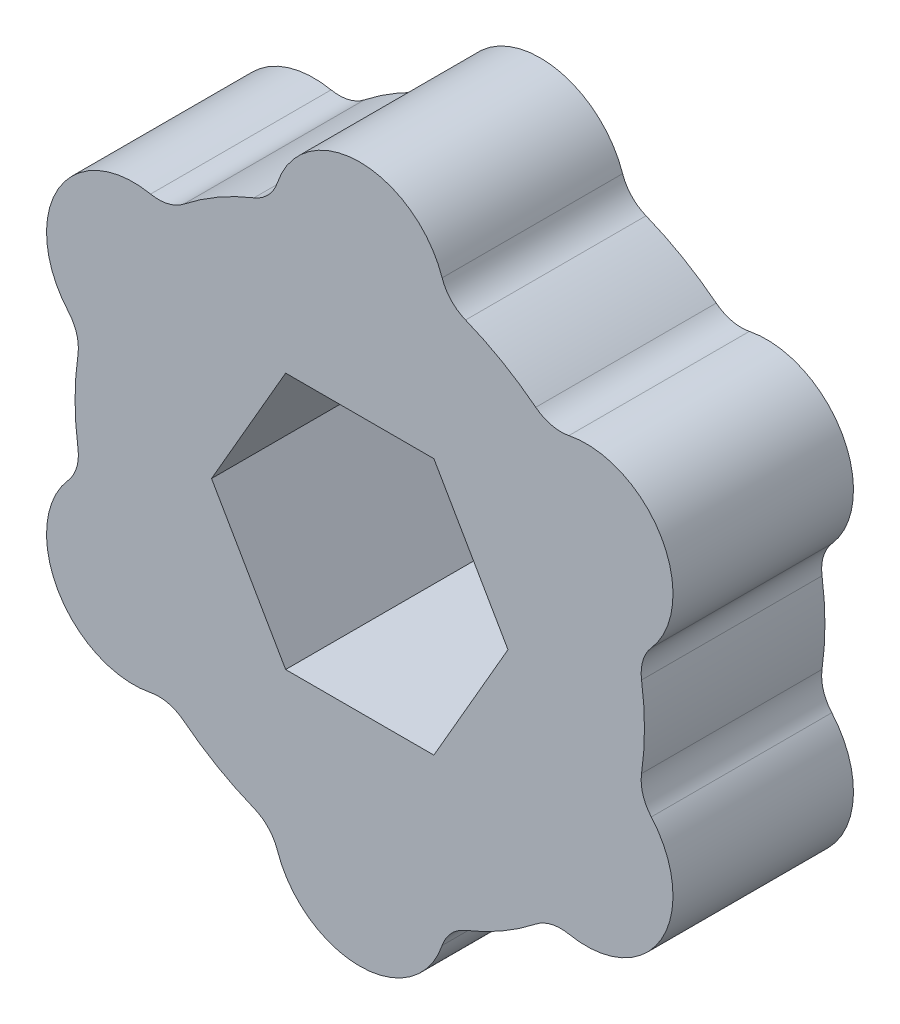
SolidWorks part; units mm, degrees
material "PET"
ref_plane "Front Plane" through (0, 0, 0) normal (0, 0, 1) x (1, 0, 0)
ref_plane "Top Plane" through (0, 0, 0) normal (0, 1, 0) x (1, 0, 0)
ref_plane "Right Plane" through (0, 0, 0) normal (1, 0, 0) x (0, 0, -1)
sketch "Sketch5" plane through (0, 0, 0) normal (0, 0, 1) x (1, 0, 0)
  line L0 (0, 0) -> (0, 13.0556) construction
  circle A0 centre (0, 0) radius 14.224
  circle A1 centre (0, 0) radius 17.399 construction
  arc A2 (-4.3147, 13.5538) -> (4.3147, 13.5538) centre (0, 13.0556) cw
  arc A3 (9.5806, 10.5136) -> (13.8953, 3.0402) centre (11.3065, 6.5278) cw
  arc A4 (13.8953, -3.0402) -> (9.5806, -10.5136) centre (11.3065, -6.5278) cw
  arc A5 (4.3147, -13.5538) -> (-4.3147, -13.5538) centre (0, -13.0556) cw
  arc A6 (-9.5806, -10.5136) -> (-13.8953, -3.0402) centre (-11.3065, -6.5278) cw
  arc A7 (-13.8953, 3.0402) -> (-9.5806, 10.5136) centre (-11.3065, 6.5278) cw
  point P24 (0, 0)
  dimension "D1" = 28.448
  dimension "D2" = 34.798
  dimension "D3" = 4.3434
  dimension "D4" = 6
extrude "Boss-Extrude2" add sketch "Sketch5" along normal blind 9.017 contours A7 A0 | A2 A0 | A3 A0 | A4 A0 | A5 A0 | A6 A0 | A0 region at (13.3495, 7.7073, 0) region at (13.3495, -7.7073, 0) region at (0, 15.4147, 0) region at (0, -15.4147, 0) region at (-13.3495, 7.7073, 0) region at (-13.3495, -7.7073, 0)
fillet "Fillet1" radius 2.032 12 edges at (-9.5806, 10.5136, 4.5085) (-4.3147, 13.5538, 4.5085) (4.3147, 13.5538, 4.5085) (9.5806, 10.5136, 4.5085) (13.8953, 3.0402, 4.5085) (13.8953, -3.0402, 4.5085) (9.5806, -10.5136, 4.5085) (4.3147, -13.5538, 4.5085) (-4.3147, -13.5538, 4.5085) (-9.5806, -10.5136, 4.5085) (-13.8953, -3.0402, 4.5085) (-13.8953, 3.0402, 4.5085)
sketch "Sketch6" plane through (0, 0, 9.017) normal (0, 0, 1) x (1, 0, 0)
  line L1 (7.4057, 0) -> (3.7028, 6.4135)
  line L2 (3.7028, 6.4135) -> (-3.7028, 6.4135)
  line L3 (-3.7028, 6.4135) -> (-7.4057, 0)
  line L4 (-7.4057, 0) -> (-3.7028, -6.4135)
  line L5 (-3.7028, -6.4135) -> (3.7028, -6.4135)
  line L6 (3.7028, -6.4135) -> (7.4057, 0)
  circle A0 centre (0, 0) radius 6.4135 construction
  dimension "D1" = 12.827
extrude "Cut-Extrude1" cut sketch "Sketch6" against normal through all
sketch "Sketch7" plane through (0, 0, 0) normal (0, 0, -1) x (-1, 0, 0)
  line L0 (-7.4057, 0) -> (-3.7028, 6.4135) construction
  line L1 (-3.7028, -6.4135) -> (-7.4057, 0) construction
  line L2 (3.7028, -6.4135) -> (-3.7028, -6.4135) construction
  line L3 (7.4057, 0) -> (3.7028, -6.4135) construction
  line L4 (3.7028, 6.4135) -> (7.4057, 0) construction
  line L5 (-3.7028, 6.4135) -> (3.7028, 6.4135) construction
  line L6 (-7.4057, 0) -> (-3.7028, 6.4135)
  line L7 (-3.7028, -6.4135) -> (-7.4057, 0)
  line L8 (3.7028, -6.4135) -> (-3.7028, -6.4135)
  line L9 (7.4057, 0) -> (3.7028, -6.4135)
  line L10 (3.7028, 6.4135) -> (7.4057, 0)
  line L11 (-3.7028, 6.4135) -> (3.7028, 6.4135)
  circle A0 centre (0, 0) radius 9.525
  dimension "D1" = 19.05
extrude "Boss-Extrude3" add sketch "Sketch7" along normal blind 1.778
equation "\"D1@Boss-Extrude2\"=0.335000in+0.02000"
equation "\"D1@Boss-Extrude3\"=0.150000in-0.06250"
